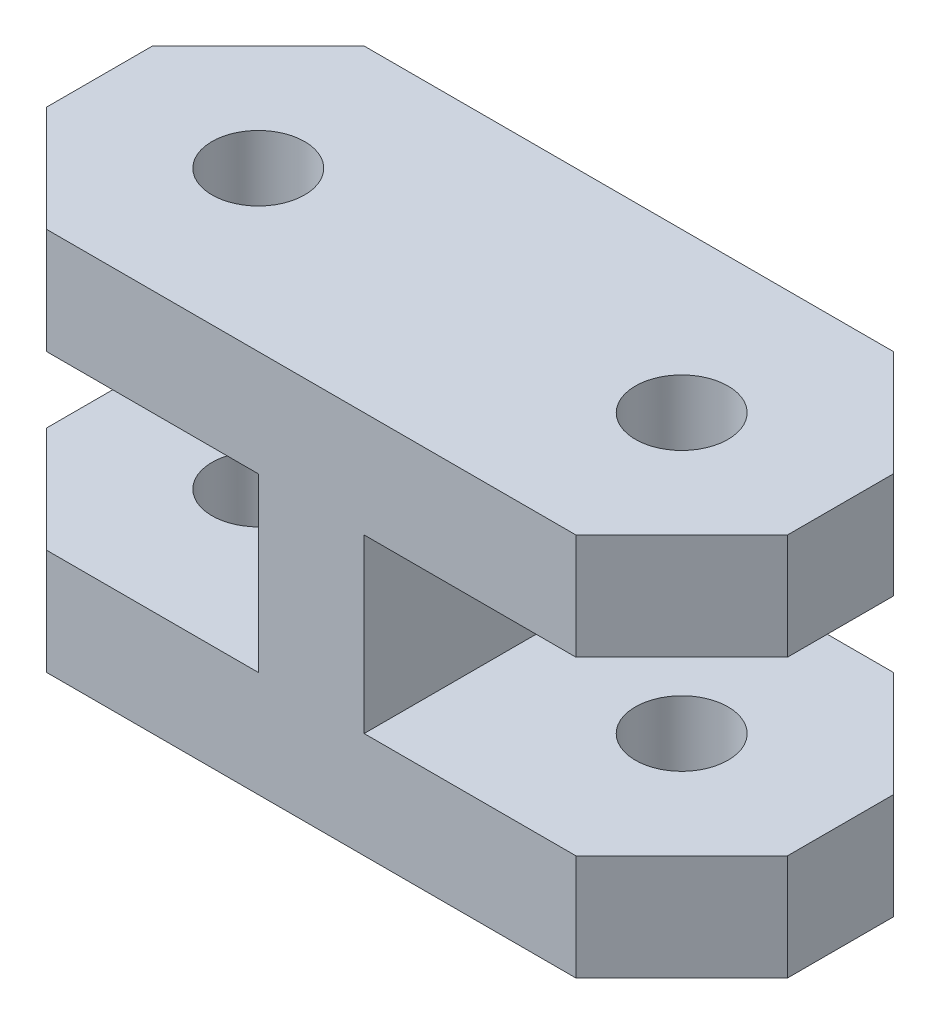
SolidWorks part; units mm, degrees
ref_plane "Front Plane" through (0, 0, 0) normal (0, 0, 1) x (1, 0, 0)
ref_plane "Top Plane" through (0, 0, 0) normal (0, 1, 0) x (1, 0, 0)
ref_plane "Right Plane" through (0, 0, 0) normal (1, 0, 0) x (0, 0, -1)
sketch "Sketch1" plane through (0, 0, 0) normal (0, 0, 1) x (1, 0, 0)
  line L0 (0, 0) -> (12, 0)
  line L1 (16, 0) -> (16, -6.5)
  line L2 (12, -6.5) -> (0, -6.5)
  line L3 (0, -6.5) -> (0, -10.5)
  line L4 (0, -10.5) -> (28, -10.5)
  line L5 (28, -10.5) -> (28, -6.5)
  line L6 (28, -6.5) -> (16, -6.5)
  line L7 (12, -6.5) -> (12, 0)
  line L8 (16, 0) -> (28, 0)
  line L9 (28, 0) -> (28, 4)
  line L10 (28, 4) -> (0, 4)
  line L11 (0, 4) -> (0, 0)
  dimension "D1" = 4
  dimension "D2" = 6.5
  dimension "D3" = 12
  dimension "D4" = 4
extrude "Boss-Extrude1" add sketch "Sketch1" along normal blind 12
sketch "Sketch2" plane through (0, 0, 0) normal (0, -1, 0) x (-1, 0, 0)
  line L0 (-28, -12) -> (-16, 0) construction
  line L1 (-16, 0) -> (-12, 0) construction
  line L2 (-12, 0) -> (0, -12) construction
  circle A0 centre (-6, -6) radius 1.75
  circle A1 centre (-22, -6) radius 1.75
  dimension "D1" = 3.5
extrude "Cut-Extrude1" cut sketch "Sketch2" against normal through all both and the other way through all
chamfer "Chamfer1" distance 4 angle 45 8 edges at (0, -8.5, 12) (0, -8.5, 0) (0, 2, 0) (0, 2, 12) (28, -8.5, 12) (28, -8.5, 0) (28, 2, 0) (28, 2, 12)
